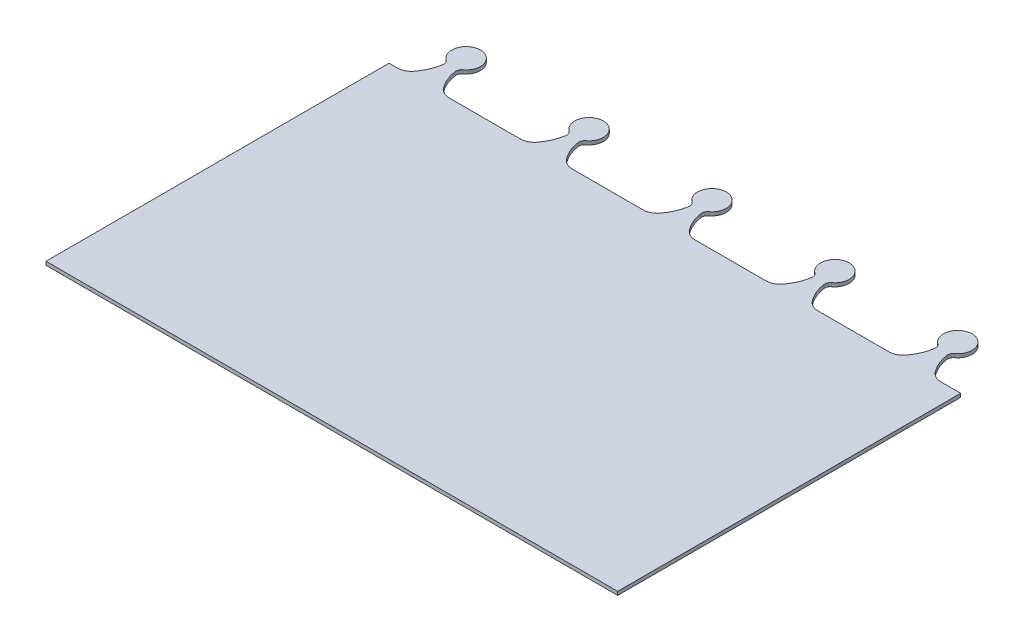
SolidWorks part; units mm, degrees
ref_plane "Front Plane" through (0, 0, 0) normal (0, 0, 1) x (1, 0, 0)
ref_plane "Top Plane" through (0, 0, 0) normal (0, 1, 0) x (1, 0, 0)
ref_plane "Right Plane" through (0, 0, 0) normal (1, 0, 0) x (0, 0, -1)
sketch "Sketch1" plane through (0, 0, 0) normal (0, 1, 0) x (1, 0, 0)
  line L0 (30.4307, 342.9) -> (30.4307, 321.747) construction
  line L1 (0, 0) -> (508, 0)
  line L2 (0, 0) -> (0, 304.8)
  line L3 (0, 304.8) -> (7.2682, 304.8)
  line L4 (508, 0) -> (508, 304.8)
  line L5 (53.5931, 304.8) -> (508, 304.8)
  line L6 (7.2682, 304.8) -> (53.5931, 304.8)
  arc A0 (17.2524, 309.651) -> (25.0143, 327.7904) centre (-12.7, 333.1981) ccw
  arc A1 (37.8914, 332.6225) -> (22.97, 332.6225) centre (30.4307, 342.9) ccw
  arc A2 (43.609, 309.651) -> (35.8471, 327.7904) centre (73.5614, 333.1981) cw
  arc A3 (35.8471, 327.7904) -> (37.8914, 332.6225) centre (40.8757, 328.5114) cw
  arc A4 (25.0143, 327.7904) -> (22.97, 332.6225) centre (19.9857, 328.5114) ccw
  arc A5 (43.609, 309.651) -> (53.5931, 304.8) centre (53.5931, 317.5) ccw
  arc A6 (17.2524, 309.651) -> (7.2682, 304.8) centre (7.2682, 317.5) cw
  point P15 (35.5107, 331.2603)
  point P18 (25.3507, 331.2603)
  point P21 (48.1614, 304.8)
  point P24 (12.7, 304.8)
  dimension "D4" = 38.1
  dimension "D5" = 25.4
  dimension "D9" = 5.08
  dimension "D7" = 38.1
  dimension "D10" = 12.7
  dimension "D1" = 304.8
  dimension "D2" = 508
  dimension "D3" = 12.7
  dimension "D6" = 5.08
  dimension "D8" = 12.7
extrude "Boss-Extrude1" add sketch "Sketch1" along normal blind 3.175 contours L1 L4 L3 L2 region at (254, 0, -152.4)
extrude "Boss-Extrude2" add sketch "Sketch1<3>" along normal blind 3.175 contours L3 A2 A1 A0 region at (30.4307, 0, -329.0681)
sketch "Sketch1<3>" plane through (0, 0, 0) normal (0, 1, 0) x (1, 0, 0) same geometry as "Sketch1"
pattern_linear "LPattern1" count 5 spacing 109.22 along (1, 0, 0) of "Boss-Extrude2"
